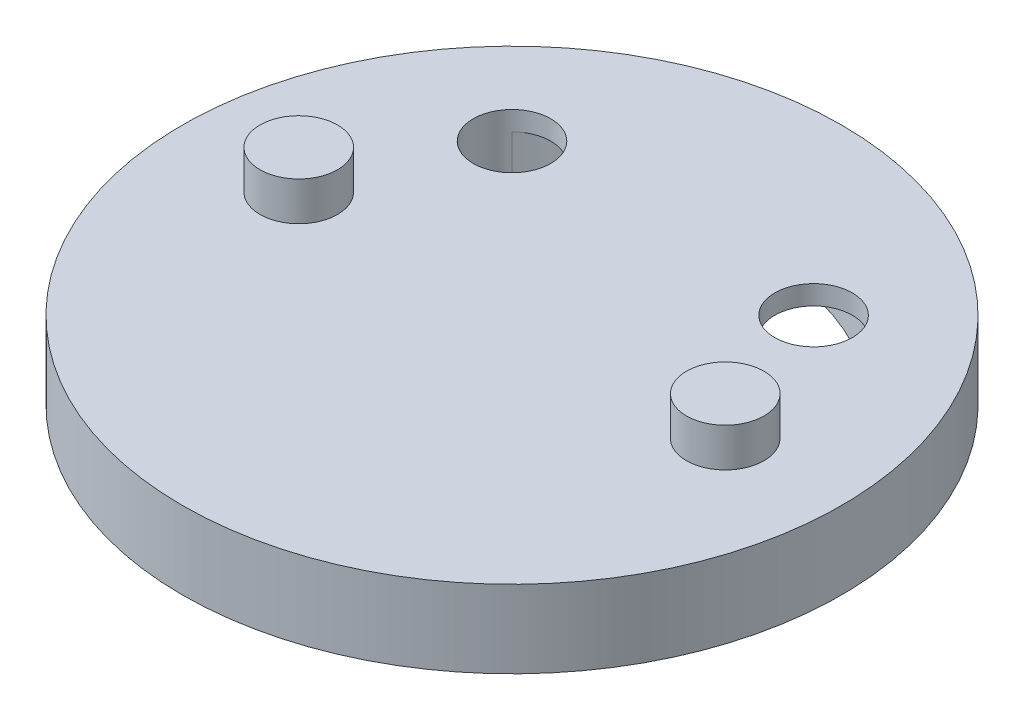
SolidWorks part; units mm, degrees
ref_plane "前视基准面" through (0, 0, 0) normal (0, 0, 1) x (1, 0, 0)
ref_plane "上视基准面" through (0, 0, 0) normal (0, 1, 0) x (1, 0, 0)
ref_plane "右视基准面" through (0, 0, 0) normal (1, 0, 0) x (0, 0, -1)
other "Configuration Table"
sketch "草图1" plane through (0, 0, 0) normal (0, 1, 0) x (1, 0, 0)
  circle A0 centre (0, 0) radius 17
  dimension "D1" = 34
extrude "凸台-拉伸1" add sketch "草图1" along normal blind 4
sketch "草图2" plane through (0, 4, 0) normal (0, 1, 0) x (1, 0, 0)
  line L0 (0, 0) -> (0, 11) construction
  circle A0 centre (0, 0) radius 11 construction
  circle A1 centre (-11, 0) radius 2
  circle A2 centre (-7.7782, 7.7782) radius 2
  circle A3 centre (7.7782, 7.7782) radius 2
  circle A4 centre (11, 0) radius 2
  point P12 (0, 0)
  dimension "D1" = 22
  dimension "D2" = 4
  dimension "D3" = 45
extrude "切除-拉伸1" cut sketch "草图2" against normal blind 3 contours A2 | A3 region at (-7.7782, 4, -7.7782) region at (7.7782, 4, -7.7782)
extrude "凸台-拉伸2" add sketch "草图2<3>" along normal blind 2 contours A4 | A1 region at (-11, 4, 0) region at (11, 4, 0)
sketch "草图2<3>" plane through (0, 4, 0) normal (0, 1, 0) x (1, 0, 0) same geometry as "草图2"
sketch "草图4" plane through (0, 0, 0) normal (0, -1, 0) x (1, 0, 0)
  line L0 (0, 0) -> (17, 0) construction
  arc A0 (-7.7782, -7.7782) -> (7.7782, -7.7782) centre (0, 0) ccw construction
  arc A1 (-9.1924, -9.1924) -> (9.1924, -9.1924) centre (0, 0) ccw
  arc A2 (-6.364, -6.364) -> (6.364, -6.364) centre (0, 0) ccw
  arc A3 (-6.364, -6.364) -> (-9.1924, -9.1924) centre (-7.7782, -7.7782) ccw
  arc A4 (9.1924, -9.1924) -> (6.364, -6.364) centre (7.7782, -7.7782) ccw
  circle A5 centre (7.7782, -7.7782) radius 2 construction
  circle A6 centre (-7.7782, -7.7782) radius 2 construction
  circle A7 centre (0, 0) radius 17 construction
  arc A8 (-7.7782, 7.7782) -> (7.7782, 7.7782) centre (0, 0) cw construction
  arc A9 (-9.1924, 9.1924) -> (9.1924, 9.1924) centre (0, 0) cw
  arc A10 (-6.364, 6.364) -> (6.364, 6.364) centre (0, 0) cw
  arc A11 (-6.364, 6.364) -> (-9.1924, 9.1924) centre (-7.7782, 7.7782) cw
  arc A12 (9.1924, 9.1924) -> (6.364, 6.364) centre (7.7782, 7.7782) cw
  point P4 (0, -11)
  point P20 (0, 11)
  dimension "D1" = 2
extrude "切除-拉伸2" cut sketch "草图4" against normal blind 3
